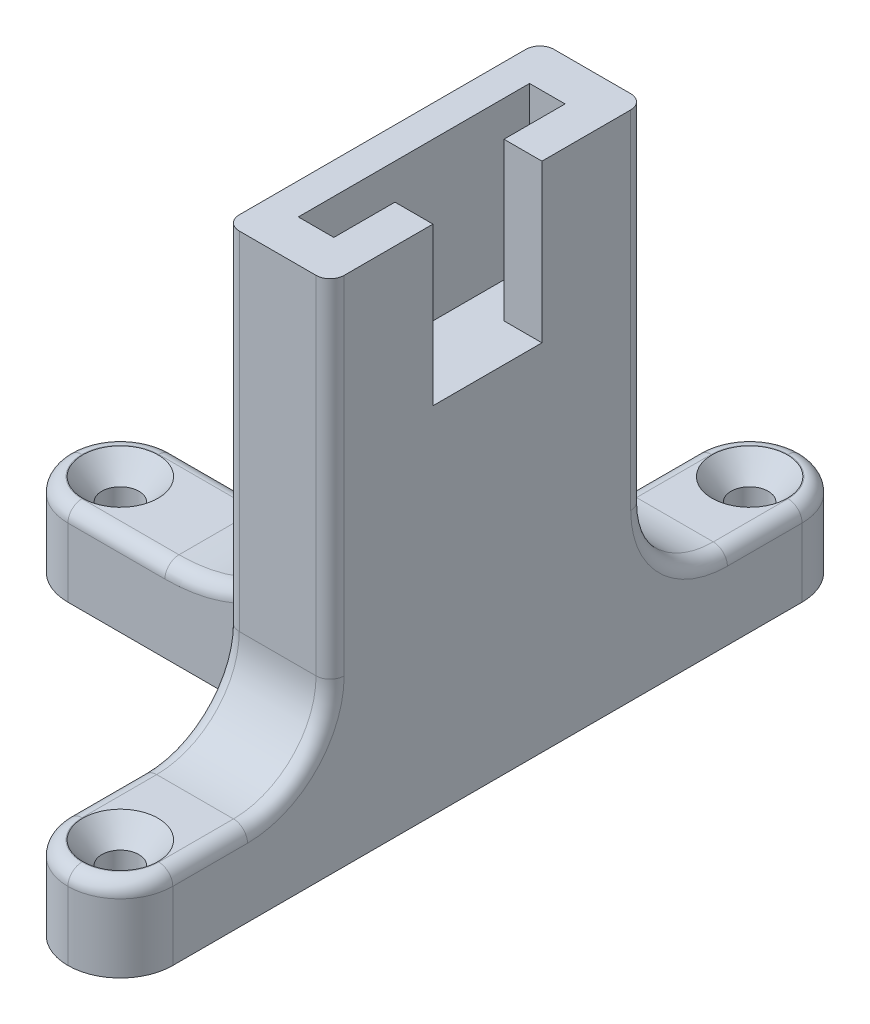
SolidWorks part; units mm, degrees
ref_plane "Front Plane" through (0, 0, 0) normal (0, 0, 1) x (1, 0, 0)
ref_plane "Top Plane" through (0, 0, 0) normal (0, 1, 0) x (1, 0, 0)
ref_plane "Right Plane" through (0, 0, 0) normal (1, 0, 0) x (0, 0, -1)
sketch "Sketch1" plane through (0, 0, 0) normal (0, 1, 0) x (1, 0, 0)
  line L1 (6.35, -19.05) -> (-6.35, -19.05)
  line L2 (6.35, -19.05) -> (6.35, 19.05)
  line L3 (6.35, 19.05) -> (-6.35, 19.05)
  line L4 (-6.35, -19.05) -> (-6.35, 19.05)
  line L5 (6.35, -19.05) -> (-6.35, 19.05) construction
  line L6 (6.35, 19.05) -> (-6.35, -19.05) construction
  point P0 (0, 0)
  dimension "D1" = 38.1
  dimension "D2" = 12.7
extrude "Boss-Extrude1" add sketch "Sketch1" along normal blind 62
sketch "Sketch2" plane through (0, 62, 0) normal (0, 1, 0) x (1, 0, 0)
  line L0 (6.35, -19.05) -> (6.35, 19.05) construction
  line L1 (1.75, -6.6) -> (6.35, -6.6)
  line L3 (1.75, 6.6) -> (6.35, 6.6)
  line L4 (6.35, -6.6) -> (6.35, 6.6)
  line L5 (1.75, 6.6) -> (1.75, 14)
  line L6 (-2.55, -14) -> (1.75, -14)
  line L7 (-2.55, -14) -> (-2.55, 14)
  line L8 (-2.55, 14) -> (1.75, 14)
  line L9 (1.75, -14) -> (1.75, -6.6)
  point P6 (6.35, 0)
  point P7 (6.35, 0)
  point P12 (-2.55, 0)
  dimension "D1" = 13.2
  dimension "D2" = 28
  dimension "D3" = 4.6
  dimension "D4" = 4.3
extrude "Cut-Extrude1" cut sketch "Sketch2" against normal blind 19.05
sketch "Sketch3" plane through (0, 0, 0) normal (0, 1, 0) x (1, 0, 0)
  line L0 (-6.35, 19.05) -> (-6.35, -19.05) construction
  line L1 (-6.35, 19.05) -> (6.35, 19.05)
  line L2 (-6.35, 19.05) -> (-6.35, 44.45)
  line L3 (-6.35, 44.45) -> (6.35, 44.45)
  line L4 (6.35, 19.05) -> (6.35, 44.45)
  line L5 (-6.35, -19.05) -> (6.35, -19.05)
  line L6 (-6.35, -19.05) -> (-6.35, -44.45)
  line L7 (-6.35, -44.45) -> (6.35, -44.45)
  line L8 (6.35, -19.05) -> (6.35, -44.45)
  line L9 (-44.45, 6.35) -> (-6.35, 6.35)
  line L10 (-44.45, 6.35) -> (-44.45, -6.35)
  line L11 (-44.45, -6.35) -> (-6.35, -6.35)
  line L12 (-6.35, 6.35) -> (-6.35, -6.35)
  line L13 (6.35, -19.05) -> (6.35, 19.05) construction
  line L14 (31.75, 6.35) -> (6.35, 6.35)
  line L15 (31.75, 6.35) -> (31.75, -6.35)
  line L16 (31.75, -6.35) -> (6.35, -6.35)
  line L17 (6.35, 6.35) -> (6.35, -6.35)
  point P18 (6.35, 0)
  point P24 (-6.35, 0)
  dimension "D1" = 25.4
  dimension "D2" = 25.4
  dimension "D3" = 12.7
  dimension "D4" = 38.1
  dimension "D5" = 25.4
  dimension "D6" = 12.7
extrude "Boss-Extrude2" add sketch "Sketch3" along normal blind 10
fillet "Fillet1" radius 10 5 edges at (6.35, 5, -6.35) (6.35, 10, 0) (6.35, 5, 6.35) (0, 10, 19.05) (0, 10, -19.05)
fillet "Fillet2" radius 20 1 edges at (-6.35, 10, 0)
fillet "Fillet3" radius 10 2 edges at (-6.35, 15, -6.35) (-6.35, 15, 6.35)
fillet "Fillet4" radius 6.35 8 edges at (-6.35, 5, -44.45) (6.35, 5, -44.45) (31.75, 5, -6.35) (31.75, 5, 6.35) (6.35, 5, 44.45) (-6.35, 5, 44.45) (-44.45, 5, -6.35) (-44.45, 5, 6.35)
sketch "Sketch4" plane through (0, 10, 0) normal (0, 1, 0) x (1, 0, 0)
  line L0 (-44.45, 0) -> (31.75, 0) construction
  line L3 (0, -44.45) -> (0, 44.45) construction
  point P12 (-38.1, 0)
  point P13 (0, -38.1)
  point P14 (25.4, 0)
  point P15 (0, 38.1)
  dimension "D1" = 6.35
  dimension "D2" = 6.35
  dimension "D3" = 6.35
hole_wizard "CSK for #8 Flat Head Socket Cap Screw1" positions "Sketch6" profile "Sketch7" countersink size "#8" standard "ANSI Inch" end condition through all
sketch "Sketch6" plane through (0, 10, 0) normal (0, 1, 0) x (1, 0, 0)
  point P0 (-38.1, 0)
  point P3 (0, -38.1)
  point P6 (25.4, 0)
  point P9 (0, 38.1)
sketch "Sketch7" plane through (-38.1, 10, 0) normal (1, 0, 0) x (0, 0, 1)
  line L0 (0, 0) -> (0, 10)
  line L1 (0, 10) -> (2.2479, 10)
  line L2 (2.2479, 10) -> (2.2479, 2.659)
  line L3 (2.2479, 2.659) -> (4.5593, 0)
  line L5 (4.5593, 0) -> (0, 0)
  line L6 (-2.2479, 2.659) -> (-4.5593, 0) construction
  line L11 (0, -6.35) -> (0, 107.95) construction
  dimension "Thru Hole Dia." = 4.4958
  dimension "Thru Hole Depth" = 10
  dimension "Near C'Sink Dia." = 9.1186
  dimension "Near C'Sink Angle" = 82
fillet "Fillet5" radius 1.7 30 edges at (6.35, 41, -19.05) (6.35, 12.9289, -21.9789) (-6.35, 41, -19.05) (-6.35, 12.9289, -21.9789) (-6.35, 10, -33.575) (-4.4901, 10, -42.5901) (4.4901, 10, -42.5901) (9.2789, 12.9289, 9.2789) (9.2789, 12.9289, -9.2789) (20.875, 10, -6.35) (29.8901, 10, -4.4901) (29.8901, 10, 4.4901) (-6.35, 41, 19.05) (-6.35, 12.9289, 21.9789) (-6.35, 10, 33.575) (6.35, 41, 19.05) (6.35, 12.9289, 21.9789) (6.35, 10, 33.575) (4.4901, 10, 42.5901) (-8.95, 20.139, -9.624) (-21.1736, 10.6815, -6.35) (-32.225, 10, -6.35) (-42.5901, 10, -4.4901) (-8.95, 20.139, 9.624) (-21.1736, 10.6815, 6.35) (-32.225, 10, 6.35) (6.35, 10, -33.575) (20.875, 10, 6.35) (-4.4901, 10, 42.5901) (-42.5901, 10, 4.4901)
sketch "Sketch8" plane through (-2.55, 0, 0) normal (1, 0, 0) x (0, 0, -1)
  line L0 (-14, 62) -> (14, 42.95) construction
  circle A0 centre (0, 52.475) radius 1.65
  dimension "D1" = 3.3
extrude "Cut-Extrude2" cut sketch "Sketch8" against normal blind 10
sketch "Sketch9" plane through (6.35, 0, 0) normal (1, 0, 0) x (0, 0, -1)
  line L1 (-28.0897, 35.9692) -> (28.9741, 35.9692)
  line L2 (-28.0897, 35.9692) -> (-28.0897, -14.6436)
  line L3 (-28.0897, -14.6436) -> (28.9741, -14.6436)
  line L4 (28.9741, 35.9692) -> (28.9741, -14.6436)
extrude "Cut-Extrude4" cut sketch "Sketch9" along normal through all
